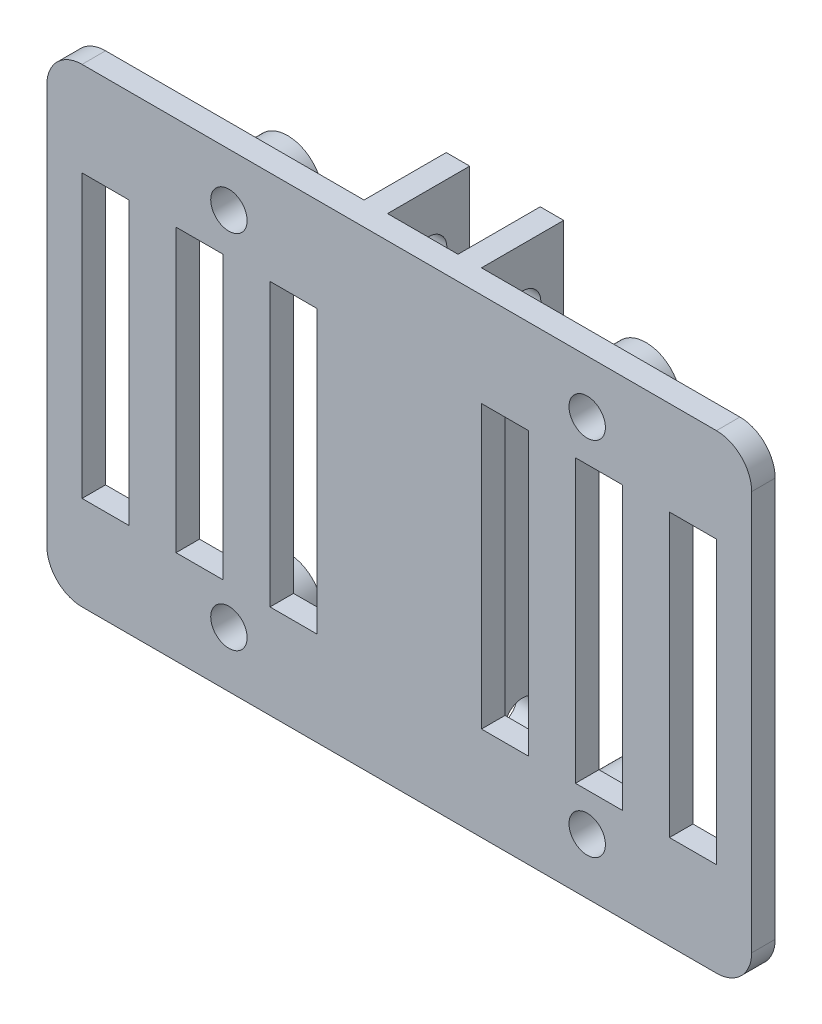
SolidWorks part; units mm, degrees
ref_plane "Plan de face" through (0, 0, 0) normal (0, 0, 1) x (1, 0, 0)
ref_plane "Plan de dessus" through (0, 0, 0) normal (0, 1, 0) x (1, 0, 0)
ref_plane "Plan de droite" through (0, 0, 0) normal (1, 0, 0) x (0, 0, -1)
sketch "Esquisse1" plane through (0, 0, 0) normal (0, 0, 1) x (1, 0, 0)
  line L1 (0, 0) -> (60, 0)
  line L2 (0, 0) -> (0, 40)
  line L3 (0, 40) -> (60, 40)
  line L4 (60, 0) -> (60, 40)
extrude "Boss.-Extru.1" add sketch "Esquisse1" along normal blind 9
sketch "Esquisse2" plane through (0, 0, 0) normal (0, 0, -1) x (-1, 0, 0)
  line L1 (-25, 40) -> (0, 40)
  line L2 (-25, 40) -> (-25, 0)
  line L3 (-25, 0) -> (0, 0)
  line L4 (0, 40) -> (0, 0)
  line L5 (-60, 40) -> (-35, 40)
  line L6 (-60, 40) -> (-60, 0)
  line L7 (-60, 0) -> (-35, 0)
  line L8 (-35, 40) -> (-35, 0)
  line L9 (-27, 40) -> (-33, 40)
  line L10 (-27, 40) -> (-27, 0)
  line L11 (-27, 0) -> (-33, 0)
  line L12 (-33, 40) -> (-33, 0)
extrude "Enlèv. mat.-Extru.1" cut sketch "Esquisse2" against normal blind 7
sketch "Esquisse3" plane through (35, 0, 0) normal (1, 0, 0) x (0, 0, -1)
  circle A0 centre (-3.5, 5) radius 1.55
  circle A1 centre (-3.5, 35) radius 1.55
  point P2 (0, 0)
  point P5 (-3.5655, 34.6493)
  point P6 (0, 0)
extrude "Enlèv. mat.-Extru.2" cut sketch "Esquisse3" against normal through all
fillet "Congé1" radius 3 4 edges at (0, 0, 8) (60, 0, 8) (0, 40, 8) (60, 40, 8)
sketch "Esquisse9" plane through (0, 0, 7) normal (0, 0, -1) x (-1, 0, 0)
  circle A1 centre (-46, 35.5) radius 3
  circle A2 centre (-15.5, 35.5) radius 3
  circle A3 centre (-15.5, 4.75) radius 3
  circle A4 centre (-46, 4.75) radius 3
extrude "Boss.-Extru.2" add sketch "Esquisse9" along normal blind 3
sketch "Esquisse5" plane through (0, 0, 7) normal (0, 0, -1) x (-1, 0, 0)
  circle A0 centre (-46, 35.5) radius 1.55
  circle A1 centre (-46, 4.75) radius 1.55
  circle A2 centre (-15.5, 4.75) radius 1.55
  circle A3 centre (-15.5, 35.5) radius 1.55
  point P8 (-13.6254, 1.6184)
  point P9 (-17.0023, 37.8719)
  point P10 (-45.6737, 1.8095)
  point P11 (0, 0)
  point P12 (0, 0)
  point P13 (0, 0)
  point P14 (0, 0)
  point P15 (0, 0)
  point P16 (0, 0)
  point P17 (0, 0)
  point P18 (0, 0)
  point P19 (0, 0)
  point P20 (0, 0)
  point P21 (0, 0)
  point P22 (0, 0)
  point P23 (0, 0)
  point P24 (0, 0)
  point P25 (0, 0)
  point P26 (0, 0)
  point P27 (0, 0)
  point P28 (0, 0)
  point P29 (0, 0)
  point P30 (0, 0)
  point P31 (0, 0)
  point P32 (0, 0)
  point P33 (0, 0)
  point P34 (0, 0)
  point P35 (0, 0)
  point P36 (0, 0)
  point P37 (0, 0)
  point P38 (0, 0)
  point P39 (0, 0)
  point P40 (0, 0)
  point P41 (0, 0)
  point P42 (0, 0)
  point P43 (0, 0)
  point P44 (0, 0)
  point P45 (0, 0)
  point P46 (0, 0)
  point P47 (0, 0)
  point P48 (0, 0)
  point P49 (0, 0)
  point P50 (0, 0)
  point P51 (0, 0)
  point P52 (0, 0)
extrude "Enlèv. mat.-Extru.4" cut sketch "Esquisse5" against normal through all both and the other way through all
sketch "Esquisse6" plane through (0, 0, 7) normal (0, 0, -1) x (-1, 0, 0)
  line L0 (-49, 32) -> (-45, 32)
  line L1 (-57, 32) -> (-53, 32)
  line L2 (-57, 32) -> (-57, 8)
  line L3 (-57, 8) -> (-53, 8)
  line L4 (-53, 32) -> (-53, 8)
  line L5 (-49, 32) -> (-49, 8)
  line L6 (-45, 32) -> (-45, 8)
  line L7 (-49, 8) -> (-45, 8)
  line L8 (-41, 32) -> (-37, 32)
  line L9 (-41, 32) -> (-41, 8)
  line L10 (-37, 32) -> (-37, 8)
  line L11 (-41, 8) -> (-37, 8)
  dimension "D1" = 3
sketch "Esquisse8" plane through (0, 0, 7) normal (0, 0, -1) x (-1, 0, 0)
  line L0 (-11, 32) -> (-11, 8)
  line L1 (-3, 32) -> (-7, 32)
  line L2 (-3, 32) -> (-3, 8)
  line L3 (-3, 8) -> (-7, 8)
  line L4 (-7, 32) -> (-7, 8)
  line L5 (-11, 32) -> (-15, 32)
  line L6 (-15, 32) -> (-15, 8)
  line L7 (-11, 8) -> (-15, 8)
  line L8 (-19, 32) -> (-19, 8)
  line L9 (-19, 32) -> (-23, 32)
  line L10 (-23, 32) -> (-23, 8)
  line L11 (-19, 8) -> (-23, 8)
  dimension "D1" = 3
extrude "Enlèv. mat.-Extru.5" cut sketch "Esquisse8" against normal blind 7
extrude "Enlèv. mat.-Extru.6" cut sketch "Esquisse6" against normal blind 7
